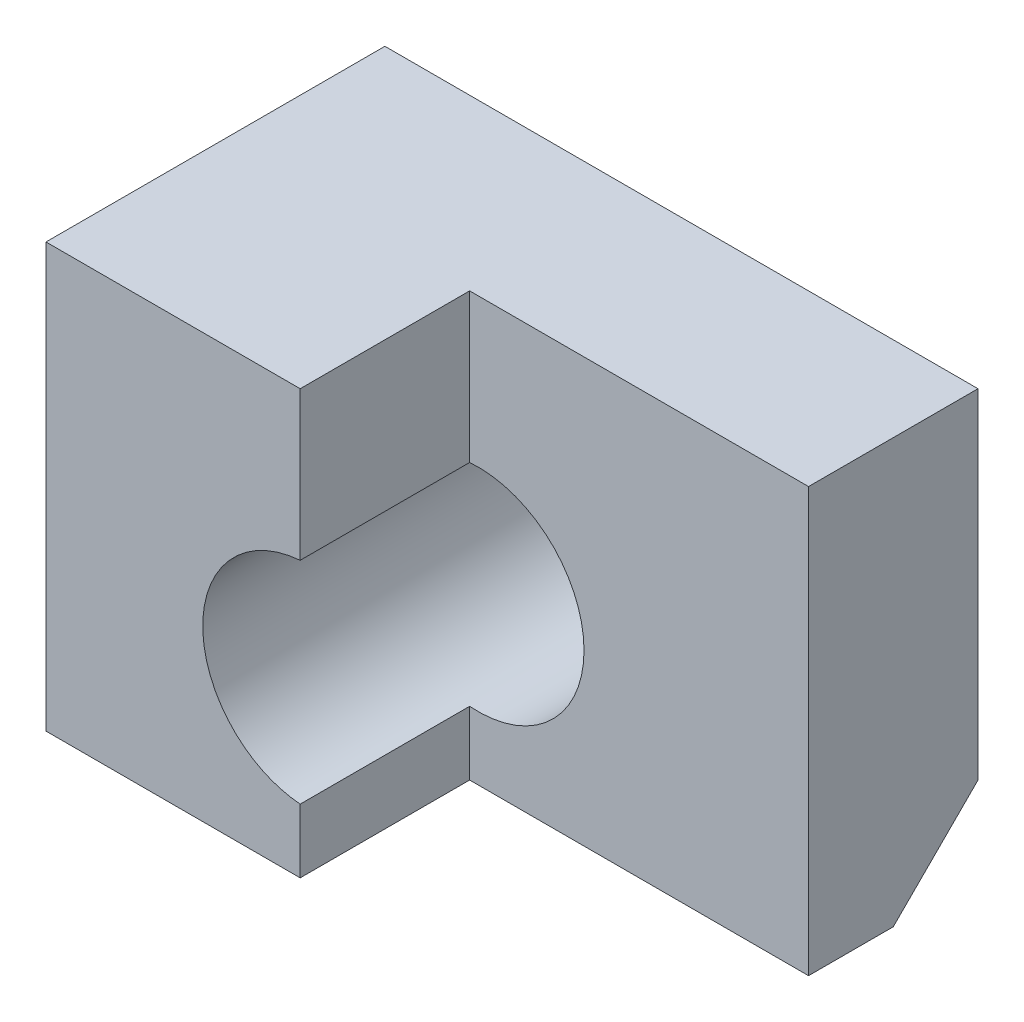
SolidWorks part; units mm, degrees
material "6061-T6 (SS)"
ref_plane "Front Plane" through (0, 0, 0) normal (0, 0, 1) x (1, 0, 0)
ref_plane "Top Plane" through (0, 0, 0) normal (0, 1, 0) x (1, 0, 0)
ref_plane "Right Plane" through (0, 0, 0) normal (1, 0, 0) x (0, 0, -1)
sketch "Sketch1" plane through (0, 0, 0) normal (0, 0, 1) x (1, 0, 0)
  line L1 (0, 0) -> (7, 0)
  line L2 (0, 0) -> (0, 5)
  line L3 (0, 5) -> (7, 5)
  line L4 (7, 0) -> (7, 5)
  dimension "D1" = 7
  dimension "D2" = 5
extrude "Boss-Extrude1" add sketch "Sketch1" along normal blind 4
sketch "Sketch3" plane through (0, 0, 0) normal (0, 0, -1) x (-1, 0, 0)
  line L0 (0, 2) -> (-3.1, 2) construction
  line L1 (0, 5) -> (0, 0) construction
  line L2 (-3.1, 2) -> (-3.1, 0) construction
  line L3 (0, 0) -> (-7, 0) construction
  dimension "D1" = 3.1
  dimension "D2" = 2
hole_wizard "M3x0.5 Tapped Hole1" positions "Sketch4" profile "Sketch5" tap size "M3x0.5" standard "ANSI Metric"
sketch "Sketch4" plane through (0, 0, 0) normal (0, 0, -1) x (-1, 0, 0)
  point P0 (-3.1, 2)
cosmetic thread "Hole Thread1" parameters "D1"=4, "D2"=3
sketch "Sketch5" plane through (3.1, 2, 0) normal (1, 0, 0) x (0, 1, 0)
  line L0 (0, 0) -> (0, 9.2511)
  line L1 (0, 9.2511) -> (1.25, 8.5)
  line L2 (1.25, 8.5) -> (1.25, 0)
  line L5 (1.25, 0) -> (0, 0)
  line L10 (0, 9.2511) -> (-1.25, 8.5) construction
  line L11 (0, -6.35) -> (0, 107.95) construction
  dimension "Tap Drill Dia." = 2.5
  dimension "Tap Drill Depth" = 8.5
  dimension "Drill Angle" = 118
sketch "Sketch6" plane through (0, 0, 4) normal (0, 0, 1) x (1, 0, 0)
  line L0 (7, 5) -> (0, 5) construction
  line L1 (7, 0) -> (3, 0)
  line L2 (7, 0) -> (7, 5)
  line L3 (7, 5) -> (3, 5)
  line L4 (3, 0) -> (3, 5)
  dimension "D1" = 4
extrude "Cut-Extrude1" cut sketch "Sketch6" against normal blind 2
chamfer "Chamfer1" distance 1 angle 45 1 edges at (3.5, 0, 0)
